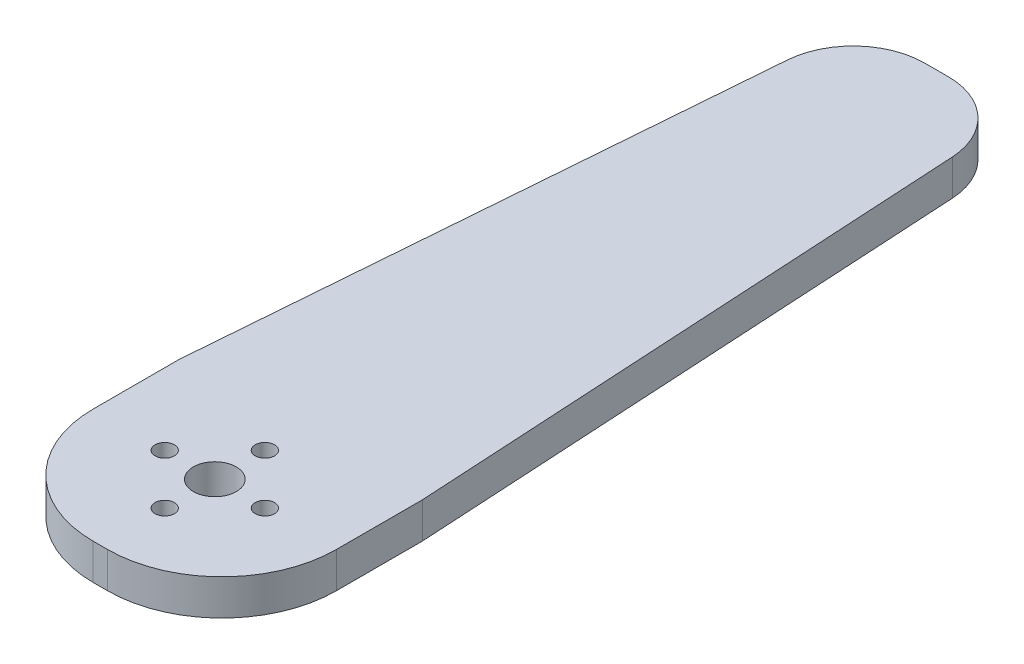
SolidWorks part; units mm, degrees
ref_plane "Front Plane" through (0, 0, 0) normal (0, 0, 1) x (1, 0, 0)
ref_plane "Top Plane" through (0, 0, 0) normal (0, 1, 0) x (1, 0, 0)
ref_plane "Right Plane" through (0, 0, 0) normal (1, 0, 0) x (0, 0, -1)
sketch "S_prism1" plane through (0, 0, 0) normal (0, 1, 0) x (1, 0, 0)
  line L0 (-1, -16) -> (1, -16)
  line L1 (17, 0) -> (17, 12)
  line L2 (17, 12) -> (12.536, 90.5673)
  line L3 (2.5521, 100) -> (-0.7639, 100)
  line L4 (-10.7324, 90.7929) -> (-17, 12)
  line L5 (-17, 12) -> (-17, 0)
  arc A0 (-17, 0) -> (-1, -16) centre (-1, 0) ccw
  arc A1 (1, -16) -> (17, 0) centre (1, 0) ccw
  arc A2 (12.536, 90.5673) -> (2.5521, 100) centre (2.552, 89.9999) ccw
  arc A3 (-0.7639, 100) -> (-10.7324, 90.7929) centre (-0.7639, 90) ccw
extrude "Boss_1" add sketch "S_prism1" along normal blind 5
ref_plane "PY_m0_100" through (0, -0.1, 0) normal (0, 1, 0) x (1, 0, 0)
sketch "S_hole2" plane through (0, -0.1, 0) normal (0, 1, 0) x (1, 0, 0)
  circle A0 centre (0, 0) radius 3
  dimension "D1_S_hole2" = 6
extrude "Hole_2" cut sketch "S_hole2" along normal blind 5.2
sketch "S_hole3" plane through (0, -0.1, 0) normal (0, 1, 0) x (1, 0, 0)
  circle A0 centre (7, 0) radius 1.35
  dimension "D1_S_hole3" = 2.7
  dimension "P2" = 7
extrude "Hole_3" cut sketch "S_hole3" along normal blind 5.2
sketch "S_hole4" plane through (0, -0.1, 0) normal (0, 1, 0) x (1, 0, 0)
  circle A0 centre (0, -7) radius 1.35
  dimension "D1_S_hole4" = 2.7
  dimension "P2" = 7
extrude "Hole_4" cut sketch "S_hole4" along normal blind 5.2
sketch "S_hole5" plane through (0, -0.1, 0) normal (0, 1, 0) x (1, 0, 0)
  circle A0 centre (-7, 0) radius 1.35
  dimension "D1_S_hole5" = 2.7
  dimension "P2" = 7
extrude "Hole_5" cut sketch "S_hole5" along normal blind 5.2
sketch "S_hole6" plane through (0, -0.1, 0) normal (0, 1, 0) x (1, 0, 0)
  circle A0 centre (0, 7) radius 1.35
  dimension "D1_S_hole6" = 2.7
  dimension "P2" = 7
extrude "Hole_6" cut sketch "S_hole6" along normal blind 5.2
equation "\"plate_t\" = 3"
equation "\"clearance\" = 0.4"
